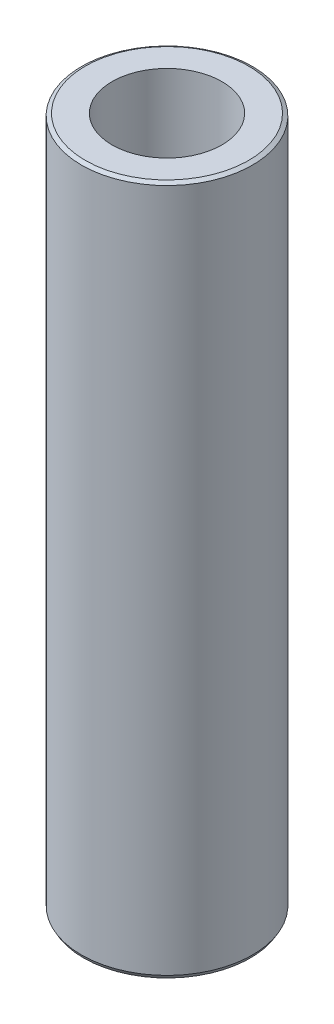
SolidWorks part; units mm, degrees
ref_plane "Front Plane" through (0, 0, 0) normal (0, 0, 1) x (1, 0, 0)
ref_plane "Top Plane" through (0, 0, 0) normal (0, 1, 0) x (1, 0, 0)
ref_plane "Right Plane" through (0, 0, 0) normal (1, 0, 0) x (0, 0, -1)
sketch "Sketch1" plane through (0, 0, 0) normal (0, 1, 0) x (1, 0, 0)
  circle A0 centre (0, 0) radius 20
  dimension "SHAFT_OD" = 40
extrude "Boss-Extrude1" add sketch "Sketch1" along normal blind 161.4136
sketch "Sketch2" plane through (0, 0, 0) normal (0, 1, 0) x (1, 0, 0)
  circle A0 centre (0, 0) radius 12.8522
  dimension "BORE_D" = 25.7044
extrude "Cut-Extrude1" cut sketch "Sketch2" along normal through all
chamfer "Chamfer1" distance 0.512 angle 60 2 edges at (0, 161.4136, 20) (0, 0, 20) first distance on face at (0, 161.4136, 20) first distance on face at (0, 0, 12.8522)
